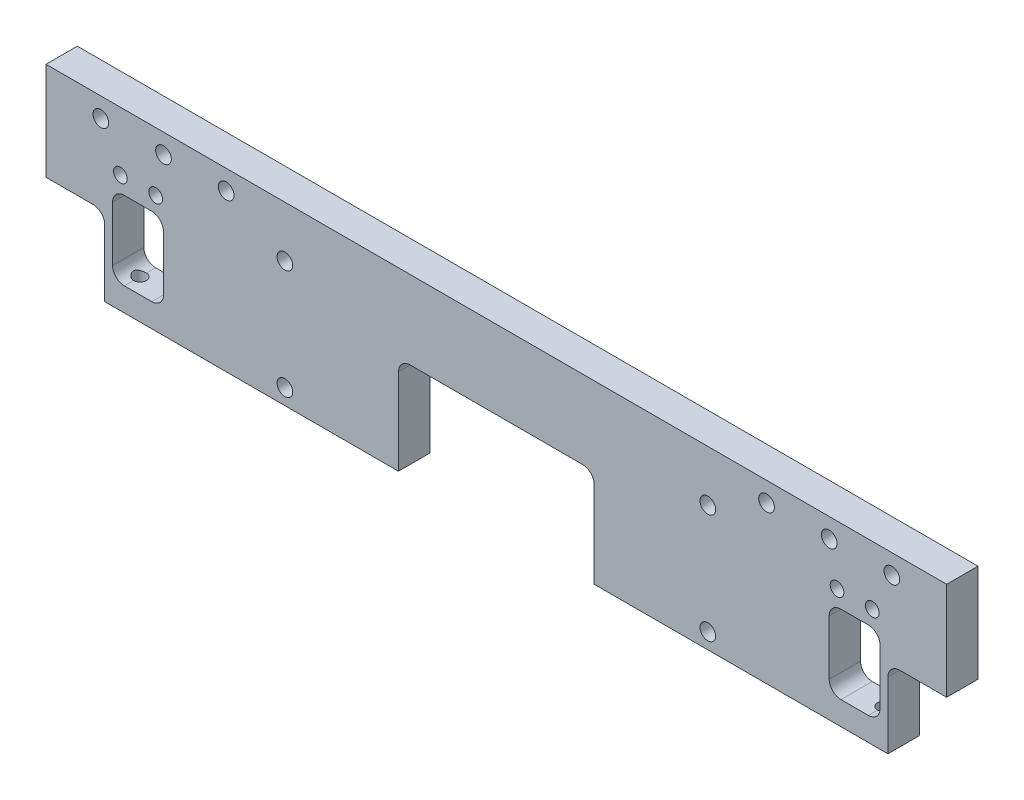
SolidWorks part; units mm, degrees
ref_plane "Front" through (0, 0, 0) normal (0, 0, 1) x (1, 0, 0)
ref_plane "Top" through (0, 0, 0) normal (0, 1, 0) x (1, 0, 0)
ref_plane "Right" through (0, 0, 0) normal (1, 0, 0) x (0, 0, -1)
sketch "Esquisse1" plane through (0, 0, 0) normal (0, 0, 1) x (1, 0, 0)
  line L1 (0, 0) -> (230, 0)
  line L2 (0, 0) -> (0, 45)
  line L3 (0, 45) -> (230, 45)
  line L4 (230, 0) -> (230, 45)
  dimension "D1" = 230
  dimension "D2" = 45
extrude "Boss.-Extru.1" add sketch "Esquisse1" along normal blind 8
sketch "Esquisse2" plane through (0, 0, 8) normal (0, 0, 1) x (1, 0, 0)
  line L0 (115, 0) -> (115, 45) construction
  line L1 (0, 0) -> (230, 0) construction
  line L2 (230, 45) -> (0, 45) construction
  line L3 (61, 4) -> (61, 32) construction
  line L4 (169, 4) -> (169, 32) construction
  circle A0 centre (61, 4) radius 2
  circle A1 centre (61, 32) radius 2
  circle A2 centre (169, 32) radius 2
  circle A3 centre (169, 4) radius 2
  dimension "D1" = 4
  dimension "D3" = 4
  dimension "D2" = 54
  dimension "D4" = 28
extrude "Enlèv. mat.-Extru.1" cut sketch "Esquisse2" against normal through all
sketch "Esquisse3" plane through (0, 0, 8) normal (0, 0, 1) x (1, 0, 0)
  line L0 (115, 0) -> (115, 32.6648) construction
  line L1 (0, 0) -> (15, 0)
  line L2 (0, 0) -> (0, 20)
  line L3 (0, 20) -> (15, 20)
  line L4 (15, 0) -> (15, 20)
  line L5 (0, 0) -> (230, 0) construction
  line L6 (215, 0) -> (215, 20)
  line L7 (230, 20) -> (215, 20)
  line L8 (230, 0) -> (230, 20)
  line L9 (230, 0) -> (215, 0)
  dimension "D1" = 20
  dimension "D2" = 15
extrude "Enlèv. mat.-Extru.2" cut sketch "Esquisse3" against normal through all
sketch "Esquisse4" plane through (0, 0, 8) normal (0, 0, 1) x (1, 0, 0)
  line L0 (14, 40) -> (46, 40) construction
  line L1 (115, 0) -> (115, 45) construction
  line L2 (15, 0) -> (215, 0) construction
  line L3 (230, 45) -> (0, 45) construction
  line L4 (216, 40) -> (184, 40) construction
  line L5 (211, 30) -> (202, 30) construction
  line L6 (19, 30) -> (28, 30) construction
  line L7 (206.5, 26) -> (206.5, 30) construction
  line L8 (200, 26) -> (213, 26)
  line L9 (200, 26) -> (200, 6)
  line L10 (200, 6) -> (213, 6)
  line L11 (213, 26) -> (213, 6)
  line L12 (17, 26) -> (17, 6)
  line L13 (30, 6) -> (17, 6)
  line L14 (30, 26) -> (30, 6)
  line L15 (30, 26) -> (17, 26)
  circle A0 centre (46, 40) radius 2
  circle A1 centre (14, 40) radius 2
  circle A2 centre (30, 40) radius 2
  circle A3 centre (200, 40) radius 2
  circle A4 centre (216, 40) radius 2
  circle A5 centre (184, 40) radius 2
  circle A6 centre (211, 30) radius 1.75
  circle A7 centre (202, 30) radius 1.75
  circle A9 centre (28, 30) radius 1.75
  circle A10 centre (19, 30) radius 1.75
  circle A11 centre (169, 4) radius 2 construction
  point P22 (208.6971, 19.9871)
  point P23 (203.584, 17.3481)
  point P38 (204.3537, 27.6842)
  point P39 (208.4771, 21.0317)
  point P42 (209.5, 25)
  point P43 (196.8216, 18.6676)
  point P44 (214.5248, 18.0079)
  point P45 (220.5725, 25)
  point P46 (205.6732, 18.0079)
  dimension "D1" = 4
  dimension "D2" = 16
  dimension "D5" = 3.5
  dimension "D7" = 33
  dimension "D3" = 40
  dimension "D4" = 170
  dimension "D6" = 9
  dimension "D8" = 30
  dimension "D9" = 20
  dimension "D10" = 13
  dimension "D11" = 4
extrude "Enlèv. mat.-Extru.3" cut sketch "Esquisse4" against normal through all
sketch "Esquisse5" plane through (0, 0, 0) normal (0, -1, 0) x (-1, 0, 0)
  line L0 (-15, -4) -> (-215, -4) construction
  line L1 (-15, 0) -> (-15, -8) construction
  line L2 (-215, 0) -> (-215, -8) construction
  line L3 (-115, -4) -> (-115, -7.2082) construction
  circle A0 centre (-155, -4) radius 1.65
  circle A1 centre (-210, -4) radius 1.65
  circle A2 centre (-20, -4) radius 1.65
  circle A3 centre (-75, -4) radius 1.65
  dimension "D1" = 3.3
  dimension "D2" = 95
  dimension "D3" = 80
extrude "Enlèv. mat.-Extru.4" cut sketch "Esquisse5" against normal blind 10
sketch "Esquisse6" plane through (0, 0, 0) normal (0, 0, -1) x (-1, 0, 0)
  line L0 (-15, 0) -> (-215, 0) construction
  line L1 (-140, 25) -> (-90, 25)
  line L2 (-140, 25) -> (-140, 0)
  line L3 (-140, 0) -> (-90, 0)
  line L4 (-90, 25) -> (-90, 0)
  line L5 (-115, 25) -> (-115, 45) construction
  line L6 (-230, 45) -> (0, 45) construction
  dimension "D1" = 50
  dimension "D2" = 25
extrude "Enlèv. mat.-Extru.5" cut sketch "Esquisse6" against normal through all
fillet "Congé1" radius 3 12 edges at (215, 20, 4) (213, 6, 4) (213, 26, 4) (200, 26, 4) (200, 6, 4) (30, 26, 4) (30, 6, 4) (17, 6, 4) (17, 26, 4) (15, 20, 4) (90, 25, 4) (140, 25, 4)
